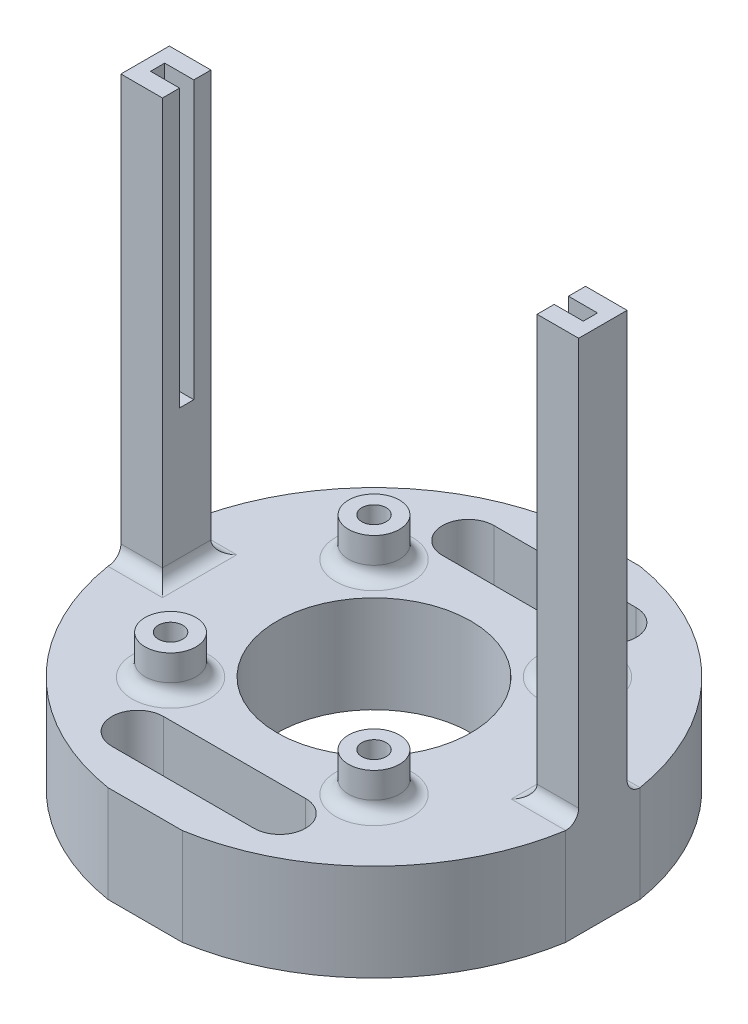
SolidWorks part; units mm, degrees
ref_plane "Front Plane" through (0, 0, 0) normal (0, 0, 1) x (1, 0, 0)
ref_plane "Top Plane" through (0, 0, 0) normal (0, 1, 0) x (1, 0, 0)
ref_plane "Right Plane" through (0, 0, 0) normal (1, 0, 0) x (0, 0, -1)
sketch "Sketch1" plane through (0, 0, 0) normal (0, 1, 0) x (1, 0, 0)
  line L1 (-13.0175, 13.0175) -> (13.0175, 13.0175) construction
  line L2 (-13.0175, 13.0175) -> (-13.0175, -13.0175) construction
  line L3 (-13.0175, -13.0175) -> (13.0175, -13.0175) construction
  line L4 (13.0175, 13.0175) -> (13.0175, -13.0175) construction
  line L5 (-13.0175, 13.0175) -> (13.0175, -13.0175) construction
  line L6 (-13.0175, -13.0175) -> (13.0175, 13.0175) construction
  line L7 (10, -10) -> (-10, -10) construction
  line L8 (10, -10) -> (10, 10) construction
  line L9 (10, 10) -> (-10, 10) construction
  line L10 (-10, -10) -> (-10, 10) construction
  line L11 (10, -10) -> (-10, 10) construction
  line L12 (10, 10) -> (-10, -10) construction
  line L13 (22.5, -22.5) -> (-22.5, -22.5)
  line L14 (22.5, -22.5) -> (22.5, 22.5)
  line L15 (22.5, 22.5) -> (-22.5, 22.5)
  line L16 (-22.5, -22.5) -> (-22.5, 22.5)
  line L17 (22.5, -22.5) -> (-22.5, 22.5) construction
  line L18 (22.5, 22.5) -> (-22.5, -22.5) construction
  point P0 (0, 0)
  point P6 (0, 0)
  point P11 (0, 0)
  dimension "D1" = 26.035
  dimension "D2" = 26.035
  dimension "D3" = 20
  dimension "D4" = 45
  dimension "D5" = 45
extrude "Boss-Extrude1" add sketch "Sketch1" against normal blind 9.525
sketch "Sketch2" plane through (0, 0, 0) normal (0, 1, 0) x (1, 0, 0)
  line L0 (0, 22.5) -> (0, -22.5) construction
  line L1 (22.5, 22.5) -> (-22.5, 22.5) construction
  line L2 (22.5, -22.5) -> (-22.5, -22.5) construction
  line L3 (-22.5, 0) -> (22.5, 0) construction
  line L4 (-22.5, -22.5) -> (-22.5, 22.5) construction
  line L5 (22.5, -22.5) -> (22.5, 22.5) construction
  circle A0 centre (-10, 10) radius 2.5
  circle A1 centre (10, 10) radius 2.5
  circle A2 centre (10, -10) radius 2.5
  circle A3 centre (-10, -10) radius 2.5
  dimension "D1" = 5
extrude "Boss-Extrude2" add sketch "Sketch2" along normal blind 3.81
sketch "Sketch3" plane through (0, 0, 0) normal (0, 1, 0) x (1, 0, 0)
  line L0 (-22.5, -22.5) -> (-22.5, 22.5) construction
  line L1 (-22.5, 2.3812) -> (-18.415, 2.3812)
  line L2 (-22.5, 2.3812) -> (-22.5, -2.3813)
  line L3 (-22.5, -2.3813) -> (-18.415, -2.3813)
  line L4 (-18.415, 2.3812) -> (-18.415, -2.3813)
  line L5 (-18.415, 0) -> (0, 0) construction
  line L6 (-13.0175, -13.0175) -> (13.0175, 13.0175) construction
  line L7 (0, 0) -> (0, 22.5) construction
  line L8 (22.5, 22.5) -> (-22.5, 22.5) construction
  line L9 (18.415, 2.3812) -> (18.415, -2.3813)
  line L10 (22.5, -2.3813) -> (18.415, -2.3813)
  line L11 (22.5, 2.3812) -> (22.5, -2.3813)
  line L12 (22.5, 2.3812) -> (18.415, 2.3812)
  dimension "D1" = 36.83
  dimension "D2" = 4.7625
extrude "Boss-Extrude3" add sketch "Sketch3" along normal blind 41.275
sketch "Sketch4" plane through (0, 41.275, 0) normal (0, 1, 0) x (1, 0, 0)
  line L0 (-22.5, 0) -> (-21.2725, 0) construction
  line L1 (-22.5, -22.5) -> (-22.5, 22.5) construction
  line L2 (21.2725, 0) -> (22.5, 0) construction
  line L3 (-21.2725, 0.6985) -> (21.2725, 0.6985)
  line L4 (-21.2725, 0.6985) -> (-21.2725, -0.6985)
  line L5 (-21.2725, -0.6985) -> (21.2725, -0.6985)
  line L6 (21.2725, 0.6985) -> (21.2725, -0.6985)
  line L7 (22.5, -22.5) -> (22.5, 22.5) construction
  dimension "D1" = 42.545
  dimension "D2" = 1.397
extrude "Cut-Extrude1" cut sketch "Sketch4" against normal blind 27.2288
fillet "Fillet1" radius 1.27 10 edges at (-10, 0, -7.5) (10, 0, -12.5) (10, 0, 12.5) (-10, 0, 7.5) (18.415, 0, 0) (20.4575, 0, -2.3812) (20.4575, 0, 2.3813) (-20.4575, 0, -2.3812) (-20.4575, 0, 2.3813) (-18.415, 0, 0)
sketch "Sketch5" plane through (0, 3.81, 0) normal (0, 1, 0) x (1, 0, 0)
  line L0 (0, 22.5) -> (0, 0) construction
  line L1 (22.5, 22.5) -> (-22.5, 22.5) construction
  line L2 (0, 0) -> (-22.5, 0) construction
  line L3 (-22.5, 2.3812) -> (-22.5, -2.3813) construction
  circle A0 centre (-10, 10) radius 1.2
  circle A1 centre (10, 10) radius 1.2
  circle A2 centre (10, -10) radius 1.2
  circle A3 centre (-10, -10) radius 1.2
  dimension "D1" = 2.4
extrude "Cut-Extrude2" cut sketch "Sketch5" against normal through all
sketch "Sketch6" plane through (0, 0, 0) normal (0, 1, 0) x (1, 0, 0)
  circle A0 centre (0, 0) radius 9.525
  dimension "D1" = 19.05
extrude "Cut-Extrude3" cut sketch "Sketch6" against normal through all
sketch "Sketch7" plane through (0, 0, 0) normal (0, 1, 0) x (1, 0, 0)
  line L0 (-3.6513, 22.5) -> (-22.5, 22.5)
  line L1 (3.6512, -22.5) -> (22.5, -22.5)
  line L12 (17.145, -3.6513) -> (17.145, 3.6513)
  line L13 (17.145, 3.6513) -> (22.5, 3.6512)
  line L14 (22.5, 3.6512) -> (22.5, 22.5)
  line L15 (22.5, 22.5) -> (-22.5, 22.5)
  line L16 (-22.5, 22.5) -> (-22.5, 3.6512)
  line L17 (-22.5, 3.6512) -> (-17.145, 3.6512)
  line L18 (-17.145, 3.6512) -> (-17.145, -3.6513)
  line L19 (-17.145, -3.6513) -> (-22.5, -3.6513)
  line L20 (-22.5, -3.6513) -> (-22.5, -22.5)
  line L21 (-22.5, -22.5) -> (22.5, -22.5)
  line L22 (22.5, -22.5) -> (22.5, -3.6513)
  line L23 (22.5, -3.6513) -> (17.145, -3.6513)
  line L26 (22.5, 3.6512) -> (22.5, 22.5)
  line L27 (22.5, 22.5) -> (3.6513, 22.5)
  line L28 (-22.5, 22.5) -> (-22.5, 3.6512)
  line L32 (-22.5, -3.6513) -> (-22.5, -22.5)
  line L33 (-22.5, -22.5) -> (-3.6512, -22.5)
  line L34 (22.5, -22.5) -> (22.5, -3.6513)
  arc A0 (-3.6513, 22.5) -> (-22.5, 3.6512) centre (0, 0) ccw
  arc A1 (3.6512, -22.5) -> (22.5, -3.6513) centre (0, 0) ccw
  arc A2 (-22.5, -3.6513) -> (-3.6512, -22.5) centre (0, 0) ccw
  arc A3 (22.5, 3.6512) -> (3.6513, 22.5) centre (0, 0) ccw
  dimension "D1" = 0
extrude "Cut-Extrude4" cut sketch "Sketch7" against normal through all
sketch "Sketch9" plane through (0, 0, 0) normal (0, 1, 0) x (1, 0, 0)
  line L0 (-10, -10) -> (10, -10) construction
  line L1 (0, -10) -> (0, -22.5) construction
  line L2 (-3.6512, -22.5) -> (3.6512, -22.5) construction
  line L3 (22.5, 0) -> (-22.5, 0) construction
  line L4 (-22.5, 2.3812) -> (-22.5, -2.3813) construction
  line L5 (-6.985, -16.25) -> (6.985, -16.25) construction
  line L6 (-6.985, -13.71) -> (6.985, -13.71)
  line L7 (-6.985, -18.79) -> (6.985, -18.79)
  line L8 (-6.985, 16.25) -> (6.985, 16.25) construction
  line L9 (-6.985, 13.71) -> (6.985, 13.71)
  line L10 (-6.985, 18.79) -> (6.985, 18.79)
  arc A0 (-6.985, -13.71) -> (-6.985, -18.79) centre (-6.985, -16.25) ccw
  arc A1 (6.985, -18.79) -> (6.985, -13.71) centre (6.985, -16.25) ccw
  arc A2 (-6.985, 13.71) -> (-6.985, 18.79) centre (-6.985, 16.25) cw
  arc A3 (6.985, 18.79) -> (6.985, 13.71) centre (6.985, 16.25) cw
  point P14 (0, 0)
  point P17 (0, -16.25)
  point P24 (0, 16.25)
  dimension "D1" = 5.08
  dimension "D2" = 13.97
extrude "Cut-Extrude5" cut sketch "Sketch9" against normal through all
